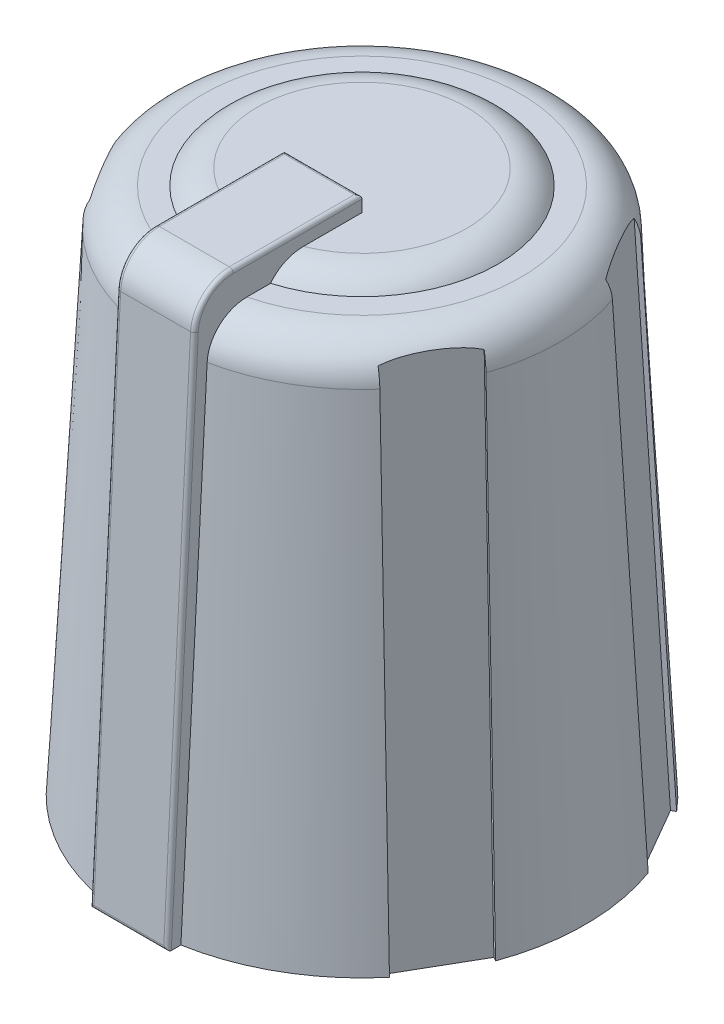
SolidWorks part; units mm, degrees
ref_plane "Front Plane" through (0, 0, 0) normal (0, 0, 1) x (1, 0, 0)
ref_plane "Top Plane" through (0, 0, 0) normal (0, 1, 0) x (1, 0, 0)
ref_plane "Right Plane" through (0, 0, 0) normal (1, 0, 0) x (0, 0, -1)
sketch "Sketch1" plane through (0, 0, 0) normal (0, 1, 0) x (1, 0, 0)
  circle A0 centre (0, 0) radius 5.75
  dimension "D1" = 11.5
extrude "Boss-Extrude1" add sketch "Sketch1" along normal blind 14 draft 3
sketch "Sketch2" plane through (0, 14, 0) normal (0, 1, 0) x (1, 0, 0)
  circle A0 centre (0, 0) radius 3.5
  dimension "D1" = 7
extrude "Cut-Extrude1" cut sketch "Sketch2" against normal blind 0.4 flip side to cut
fillet "Fillet2" radius 1 1 edges at (0, 14, 3.5)
fillet "Fillet3" radius 1 1 edges at (0, 13.6, 5.0373)
sketch "Sketch3" plane through (0, 0, 0) normal (1, 0, 0) x (0, 0, -1)
  line L0 (-6.9053, 14.2292) -> (-4.8006, 14.2292)
  line L1 (-4.8006, 14.2292) -> (-5.5815, -0.6711)
  line L2 (-5.5815, -0.6711) -> (-7.8852, -0.6711)
  line L3 (-7.8852, -0.6711) -> (-6.9053, 14.2292)
  line L4 (-5.0869, 12.6523) -> (-5.75, 0) construction
  dimension "D1" = 0.2034
extrude "Cut-Extrude2" cut sketch "Sketch3" against normal blind 1 and the other way blind 1
pattern_circular "CirPattern1" count 6 over 360 about axis through (0, 0, 0) along (0, 1, 0) of "Cut-Extrude2"
sketch "Sketch5" plane through (0, 0, 0) normal (1, 0, 0) x (0, 0, -1)
  line L0 (-5.2656, 0) -> (-4.6798, 13.1761)
  line L1 (-5.6624, 0) -> (-3.6972, 0) construction
  line L2 (-4.6798, 13.1761) -> (-1, 13.1761)
  line L3 (-1, 13.1761) -> (-1, 14.4)
  line L4 (-1, 14.4) -> (-5.2656, 14.4)
  line L5 (-5.2656, 14.4) -> (-6.0095, 0)
  line L6 (-6.0095, 0) -> (-5.2656, 0)
  line L7 (2.7, 14) -> (-2.7, 14) construction
  line L8 (0, 0) -> (0, 12.6523) construction
  dimension "D1" = 0.4
  dimension "D2" = 1
extrude "Boss-Extrude2" add sketch "Sketch5" along normal blind 1 and the other way blind 1
fillet "Fillet4" radius 1 1 edges at (0, 14.4, 5.2656)
fillet "Fillet5" radius 0.1 8 edges at (-1, 6.7258, 5.662) (-1, 14.1251, 5.0045) (1, 6.7258, 5.662) (1, 14.1251, 5.0045) (0, 0, 6.0095) (-1, 14.4, 2.6579) (0, 14.4, 1) (1, 14.4, 2.6579)
sketch "Sketch6" plane through (0, 0, 0) normal (0, -1, 0) x (1, 0, 0)
  line L0 (-1.5, 2.5981) -> (-1.5, -2.5981)
  arc A0 (-1.5, 2.5981) -> (-1.5, -2.5981) centre (0, 0) cw
  dimension "D2" = 3
  dimension "D1" = 1.5
extrude "Cut-Extrude3" cut sketch "Sketch6" against normal blind 10
